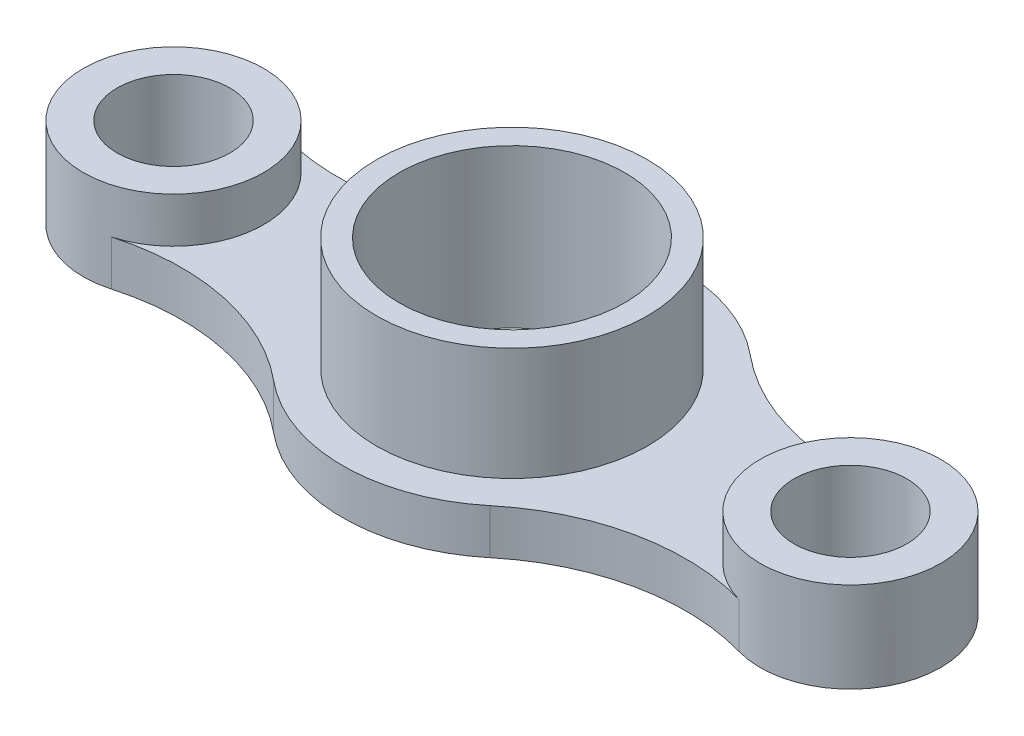
SolidWorks part; units mm, degrees
ref_plane "Front Plane" through (0, 0, 0) normal (0, 0, 1) x (1, 0, 0)
ref_plane "Top Plane" through (0, 0, 0) normal (0, 1, 0) x (1, 0, 0)
ref_plane "Right Plane" through (0, 0, 0) normal (1, 0, 0) x (0, 0, -1)
sketch "Sketch2" plane through (0, 0, 0) normal (0, 1, 0) x (1, 0, 0)
  line L0 (-127.9233, 0) -> (127.9233, 0) construction
  line L1 (0, 94.4057) -> (0, -94.4057) construction
  circle A0 centre (0, 0) radius 50
  circle A1 centre (0, 0) radius 60
  arc A2 (-47.8929, -57.7172) -> (47.8929, -57.7172) centre (0, 0) ccw
  circle A3 centre (150, 0) radius 25
  circle A4 centre (150, 0) radius 40
  arc A5 (47.8929, 57.7172) -> (139.0714, 38.4781) centre (111.75, 134.6734) ccw
  arc A6 (47.8929, -57.7172) -> (139.0714, -38.4781) centre (111.75, -134.6734) cw
  arc A7 (-47.8929, -57.7172) -> (-139.0714, -38.4781) centre (-111.75, -134.6734) ccw
  arc A8 (-47.8929, 57.7172) -> (-139.0714, 38.4781) centre (-111.75, 134.6734) cw
  circle A9 centre (-150, 0) radius 40
  circle A10 centre (-150, 0) radius 25
  arc A11 (47.8929, 57.7172) -> (-47.8929, 57.7172) centre (0, 0) ccw
  point P7 (0, 0)
  point P11 (0, 0)
  point P16 (92.1237, 166.4833)
  dimension "D1" = 150
  dimension "D2" = 100
  dimension "D3" = 120
  dimension "D4" = 80
  dimension "D5" = 50
  dimension "D8" = 200
  dimension "D6" = 150
  dimension "D7" = 0
extrude "Boss-Extrude2" add sketch "Sketch2" along normal blind 40 contours A9 A10 | A4 A3 region at (-188.8686, 0, 0) region at (111.1314, 0, 0)
extrude "Boss-Extrude3" add sketch "Sketch2<4>" along normal blind 70 separate body contours A1 A0 region at (-58.3029, 0, 0)
sketch "Sketch2<4>" plane through (0, 0, 0) normal (0, 1, 0) x (1, 0, 0) same geometry as "Sketch2"
extrude "Boss-Extrude4" add sketch "Sketch2<5>" along normal blind 20 contours A5 A11 A8 A9 A7 A2 A6 A4 A1 region at (-90.4517, 0, 33.7359)
sketch "Sketch2<5>" plane through (0, 0, 0) normal (0, 1, 0) x (1, 0, 0) same geometry as "Sketch2"
